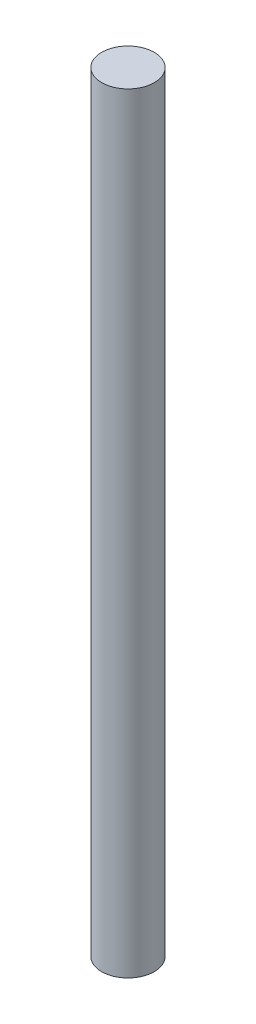
SolidWorks part; units mm, degrees
ref_plane "Front Plane" through (0, 0, 0) normal (0, 0, 1) x (1, 0, 0)
ref_plane "Top Plane" through (0, 0, 0) normal (0, 1, 0) x (1, 0, 0)
ref_plane "Right Plane" through (0, 0, 0) normal (1, 0, 0) x (0, 0, -1)
sketch "Sketch1" plane through (0, 0, 0) normal (0, 1, 0) x (1, 0, 0)
  circle A0 centre (0, 0) radius 1.25
  dimension "D1" = 2.5
extrude "Boss-Extrude1" add sketch "Sketch1" along normal blind 36.6
